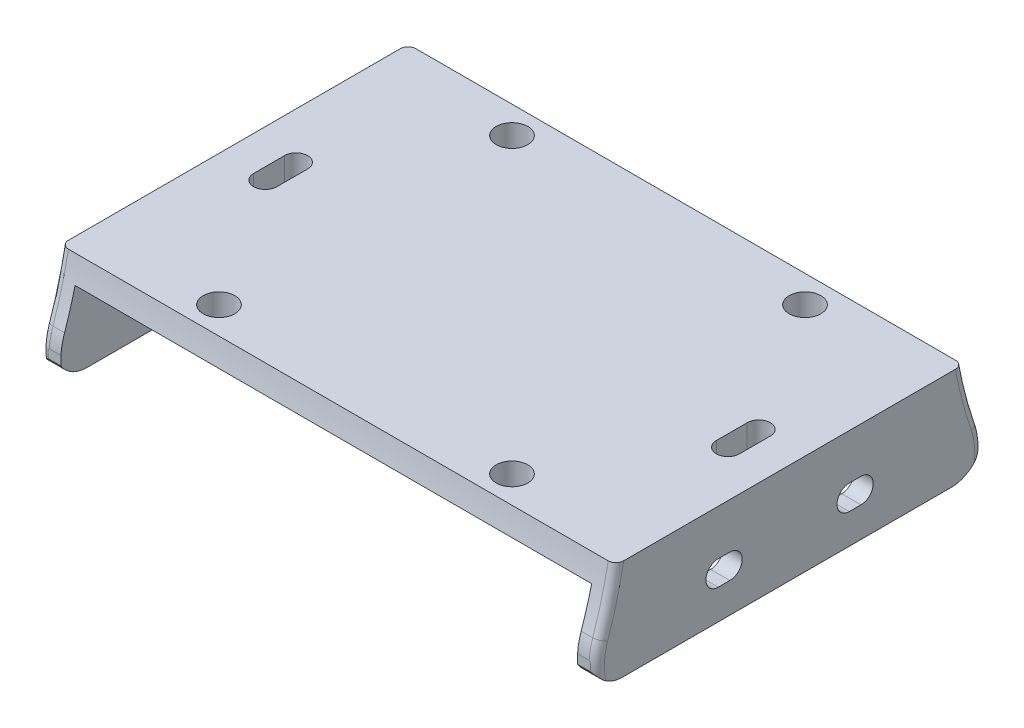
SolidWorks part; units mm, degrees
ref_plane "Front Plane" through (0, 0, 0) normal (0, 0, 1) x (1, 0, 0)
ref_plane "Top Plane" through (0, 0, 0) normal (0, 1, 0) x (1, 0, 0)
ref_plane "Right Plane" through (0, 0, 0) normal (1, 0, 0) x (0, 0, -1)
sketch "Sketch1" plane through (0, 0, 0) normal (0, 0, 1) x (1, 0, 0)
  line L0 (36.5, -28) -> (-36.5, -28) construction
  line L3 (0, -28) -> (0, -34) construction
  line L6 (-36.5, -35.5) -> (36.5, -35.5)
  line L7 (-36.5, -35.5) -> (-36.5, -32.5)
  line L8 (-36.5, -32.5) -> (36.5, -32.5)
  line L9 (36.5, -35.5) -> (36.5, -32.5)
  line L10 (-36.5, -35.5) -> (36.5, -32.5) construction
  line L11 (-36.5, -32.5) -> (36.5, -35.5) construction
  line L12 (36.5, -35.5) -> (33.5, -35.5)
  line L13 (36.5, -35.5) -> (36.5, -45.5)
  line L14 (36.5, -45.5) -> (33.5, -45.5)
  line L15 (33.5, -35.5) -> (33.5, -45.5)
  line L16 (-36.5, -35.5) -> (-33.5, -35.5)
  line L17 (-36.5, -35.5) -> (-36.5, -45.5)
  line L18 (-36.5, -45.5) -> (-33.5, -45.5)
  line L19 (-33.5, -35.5) -> (-33.5, -45.5)
  dimension "D2" = 3
  dimension "D3" = 10
  dimension "D4" = 3
extrude "Boss-Extrude1" add sketch "Sketch1" along normal up to surface (40 mm away) and the other way up to surface (10 mm away) contours L6 L9 L8 L7 | L6 L15 L14 L13 | L19 L6 L17 L18
sketch "Sketch5" plane through (0, -32.5, 0) normal (0, 1, 0) x (1, 0, 0)
  line L0 (-36.5, 10) -> (36.5, -40) construction
  line L1 (-36.5, -40) -> (36.5, 10) construction
  line L2 (0, -15) -> (-30, -15) construction
  line L3 (-19, 4) -> (19, 4) construction
  line L4 (-19, 4) -> (-19, -34) construction
  line L5 (-19, -34) -> (19, -34) construction
  line L6 (19, 4) -> (19, -34) construction
  line L7 (-19, 4) -> (19, -34) construction
  line L8 (-19, -34) -> (19, 4) construction
  line L9 (-30, -17) -> (-30, -13) construction
  line L10 (-31.5, -17) -> (-31.5, -13)
  line L11 (-28.5, -17) -> (-28.5, -13)
  line L12 (0, -15) -> (30, -15) construction
  line L13 (30, -13) -> (30, -17) construction
  line L14 (31.5, -13) -> (31.5, -17)
  line L15 (28.5, -13) -> (28.5, -17)
  circle A0 centre (-19, 4) radius 2.05
  circle A1 centre (19, 4) radius 2.05
  circle A2 centre (19, -34) radius 2.05
  circle A3 centre (-19, -34) radius 2.05
  arc A4 (-31.5, -17) -> (-28.5, -17) centre (-30, -17) ccw
  arc A5 (-28.5, -13) -> (-31.5, -13) centre (-30, -13) ccw
  arc A6 (31.5, -13) -> (28.5, -13) centre (30, -13) ccw
  arc A7 (28.5, -17) -> (31.5, -17) centre (30, -17) ccw
  point P8 (0, -15)
  point P21 (-30, -15)
  point P29 (30, -15)
  dimension "D3" = 4.1
  dimension "D6" = 1.5
  dimension "D1" = 38
  dimension "D2" = 38
  dimension "D4" = 30
  dimension "D5" = 4
extrude "Cut-Extrude2" cut sketch "Sketch5" against normal blind 5.1
sketch "Sketch8" plane through (-36.5, 0, 0) normal (-1, 0, 0) x (0, 0, 1)
  line L0 (15, -32.5) -> (15, -45.5) construction
  line L1 (40, -32.5) -> (-10, -32.5) construction
  line L2 (40, -45.5) -> (-10, -45.5) construction
  line L3 (15, -40) -> (6.5, -40) construction
  line L4 (5.75, -40) -> (7.25, -40) construction
  line L5 (5.75, -38.4) -> (7.25, -38.4)
  line L6 (5.75, -41.6) -> (7.25, -41.6)
  line L7 (24.25, -40) -> (22.75, -40) construction
  line L8 (24.25, -38.4) -> (22.75, -38.4)
  line L9 (24.25, -41.6) -> (22.75, -41.6)
  arc A0 (5.75, -38.4) -> (5.75, -41.6) centre (5.75, -40) ccw
  arc A1 (7.25, -41.6) -> (7.25, -38.4) centre (7.25, -40) ccw
  arc A2 (24.25, -38.4) -> (24.25, -41.6) centre (24.25, -40) cw
  arc A3 (22.75, -41.6) -> (22.75, -38.4) centre (22.75, -40) cw
  point P10 (6.5, -40)
  point P23 (23.5, -40)
  dimension "D1" = 1.6
  dimension "D2" = 1.5
  dimension "D3" = 8.5
  dimension "D4" = 7.5
extrude "Cut-Extrude3" cut sketch "Sketch8" against normal blind 82
sketch "Sketch9" plane through (-36.5, 0, 0) normal (-1, 0, 0) x (0, 0, 1)
  line L1 (-10, -32.5) -> (40, -32.5)
  line L2 (-10, -32.5) -> (-10, -45.5)
  line L3 (-10, -45.5) -> (40, -45.5)
  line L4 (40, -32.5) -> (40, -45.5)
extrude "Cut-Extrude4" cut sketch "Sketch9" against normal blind 0.5
mirror "Mirror1" about plane through (0, 0, 0) normal (1, 0, 0) of "Cut-Extrude4"
ref_plane "Plane1" through (0, 0, 15) normal (0, 0, 1) x (1, 0, 0)
sketch "Sketch10" plane through (36, 0, 0) normal (1, 0, 0) x (0, 0, -1)
  line L0 (-40, -32.5) -> (10, -32.5) construction
  line L1 (10, -45.5) -> (-40, -45.5) construction
  line L2 (-39.6731, -45.5) -> (-40.6676, -46.5502)
  line L3 (-40.6676, -46.5502) -> (-44.6322, -43)
  line L4 (-44.6322, -43) -> (-42.0185, -33.9807)
  line L5 (-42.0185, -33.9807) -> (-39.4635, -29.9279)
  line L6 (-39.4635, -29.9279) -> (-37.5242, -32.5)
  arc A0 (-37.5242, -32.5) -> (-39.532, -40.1351) centre (-88.8245, -23.0907) cw
  arc A2 (-39.532, -40.1351) -> (-39.6731, -45.5) centre (-31.1301, -43.0403) ccw
extrude "Cut-Extrude5" cut sketch "Sketch10" against normal blind 98.5
fillet "Fillet2" radius 4 4 edges at (34.75, -45.5, -10) (34.75, -45.5, 39.6731) (-34.75, -45.5, -10) (-34.75, -45.5, 39.6731)
mirror "Mirror2" about plane through (0, 0, 15) normal (0, 0, 1) of "Cut-Extrude5"
fillet "Fillet3" radius 1 8 edges at (36, -41.075, -9.8002) (36, -41.273, 39.8427) (-36, -41.075, -9.8002) (-36, -41.273, 39.8427) (36, -36.3556, -8.3834) (36, -36.3556, 38.3834) (-36, -36.3556, -8.3834) (-36, -36.3556, 38.3834)
